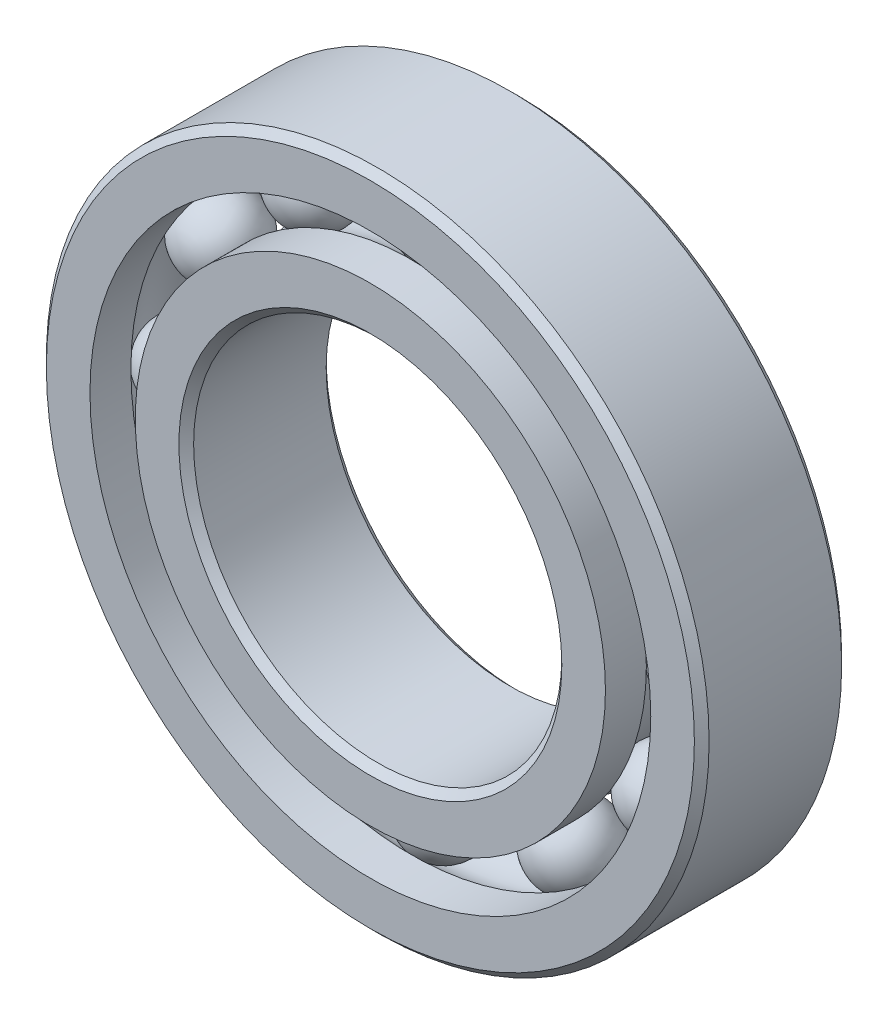
SolidWorks part; units mm, degrees
ref_plane "Front Plane" through (0, 0, 0) normal (0, 0, 1) x (1, 0, 0)
ref_plane "Top Plane" through (0, 0, 0) normal (0, 1, 0) x (1, 0, 0)
ref_plane "Right Plane" through (0, 0, 0) normal (1, 0, 0) x (0, 0, -1)
sketch "Sketch1" plane through (0, 0, 0) normal (1, 0, 0) x (0, 0, -1)
  line L0 (-10, 0) -> (10, 0) construction
  line L1 (0, 45) -> (0, -45) construction
  line L2 (9, 45) -> (-9, 45)
  line L3 (-9, 45) -> (-10, 44)
  line L4 (-10, 44) -> (-10, 38.0769)
  line L5 (-10, 38.0769) -> (-4.4444, 38.0769)
  line L6 (10, 38.0769) -> (4.4444, 38.0769)
  line L7 (10, 44) -> (10, 38.0769)
  line L8 (9, 45) -> (10, 44)
  line L9 (0, 45) -> (0, 35) construction
  line L10 (0, 35) -> (0, 25) construction
  arc A0 (-4.4444, 38.0769) -> (4.4444, 38.0769) centre (0, 35) cw
  point P14 (0, 25)
  dimension "D3" = 8.8889
  dimension "D1" = 45
  dimension "Width" = 20
  dimension "OD" = 90
  dimension "D2" = 1
  dimension "Shaft Dia" = 50
  dimension "D4" = 3.0769
revolve "Revolve1" add sketch "Sketch1" angle 360 about L0
sketch "Sketch3" plane through (0, 0, 0) normal (1, 0, 0) x (0, 0, -1)
  line L0 (-10, 31.9231) -> (-4.4444, 31.9231)
  line L1 (0, 45) -> (0, -45) construction
  line L2 (-10, 44) -> (-10, 38.0769) construction
  line L3 (-10, 31.9231) -> (-10, 26)
  line L4 (-9, 45) -> (-10, 44) construction
  line L5 (-10, 26) -> (-9, 25)
  line L6 (-9, 25) -> (9, 25)
  line L7 (9, 45) -> (9, -45) construction
  line L8 (9, 25) -> (10, 26)
  line L9 (10, -44) -> (10, 44) construction
  line L10 (10, 26) -> (10, 31.9231)
  line L11 (10, 31.9231) -> (4.4444, 31.9231)
  line L13 (9, 45) -> (10, 44) construction
  arc A0 (4.4444, 38.0769) -> (-4.4444, 38.0769) centre (0, 35) ccw construction
  arc A1 (4.4444, 31.9231) -> (-4.4444, 31.9231) centre (0, 35) cw
revolve "Revolve3" add sketch "Sketch3" angle 360 about L0
sketch "Sketch4" plane through (0, 0, 0) normal (1, 0, 0) x (0, 0, -1)
  line L0 (-5.4056, 35) -> (5.4056, 35)
  arc A2 (-5.4056, 35) -> (5.4056, 35) centre (0, 35) cw
  arc A3 (4.4444, 38.0769) -> (-4.4444, 38.0769) centre (0, 35) ccw construction
revolve "Revolve4" add sketch "Sketch4" angle 360 about L0
ref_axis "Axis1" through (0, 0, -10) along (0, 0, 1)
pattern_circular "CirPattern1" count 12 every 30 about axis through (0, 0, -10) along (0, 0, 1) of bodies 104
sketch "Sketch5" plane through (0, 0, 0) normal (1, 0, 0) x (0, 0, -1)
  line L0 (-10, 38.0769) -> (-4.4444, 38.0769) construction
  line L1 (-9.5, 38.0769) -> (-5.4056, 38.0769)
  line L2 (-9.5, 38.0769) -> (-9.5, 31.9231)
  line L3 (-9.5, 31.9231) -> (-5.4056, 31.9231)
  line L4 (-5.4056, 38.0769) -> (-5.4056, 31.9231)
  line L5 (-10, 31.9231) -> (-4.4444, 31.9231) construction
  line L6 (10, 38.0769) -> (4.4444, 38.0769) construction
  line L7 (9.5, 38.0769) -> (5.4056, 38.0769)
  line L8 (9.5, 38.0769) -> (9.5, 31.9231)
  line L9 (9.5, 31.9231) -> (5.4056, 31.9231)
  line L10 (5.4056, 38.0769) -> (5.4056, 31.9231)
  line L11 (10, 31.9231) -> (4.4444, 31.9231) construction
  line L12 (-9, 45) -> (-10, 44) construction
  point P18 (-9.5, 44.5)
revolve "Revolve5" [suppressed] add sketch "Sketch5" angle 360 about L0
equation "\"D2@Sketch1\" = \"Width@Sketch1\"*.05"
equation "\"D3@Sketch1\" = \"Width@Sketch1\"/2.25"
equation "\"D4@Sketch1\" = (((\"OD@Sketch1\"-\"Width@Sketch1\")/2)/3.25)/3.5"
equation "\"D2@CirPattern1\" = 360/\"Balls@CirPattern1\""
